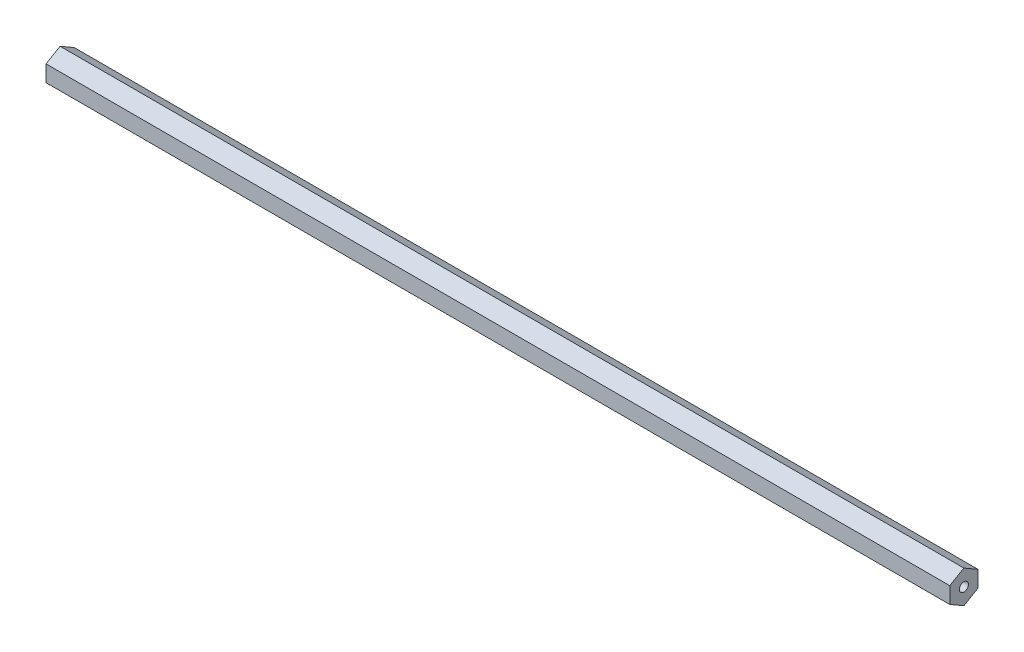
SolidWorks part; units mm, degrees
material "6061-T6 (SS)"
ref_plane "Front" through (0, 0, 0) normal (0, 0, 1) x (1, 0, 0)
ref_plane "Top" through (0, 0, 0) normal (0, 1, 0) x (1, 0, 0)
ref_plane "Right" through (0, 0, 0) normal (1, 0, 0) x (0, 0, -1)
ref_axis "Axis1" through (-80.9, 0, 0) along (1, 0, 0)
sketch "Sketch1" plane through (0, 0, 0) normal (1, 0, 0) x (0, 0, -1)
  line L1 (0, 7.3323) -> (-6.35, 3.6662)
  line L2 (-6.35, 3.6662) -> (-6.35, -3.6662)
  line L3 (-6.35, -3.6662) -> (0, -7.3323)
  line L4 (0, -7.3323) -> (6.35, -3.6662)
  line L5 (6.35, -3.6662) -> (6.35, 3.6662)
  line L6 (6.35, 3.6662) -> (0, 7.3323)
  circle A0 centre (0, 0) radius 6.35 construction
  dimension "D1" = 12.7
extrude "Boss-Extrude1" add sketch "Sketch1" along normal mid plane 406.4
hole_wizard "#10-32 Tapped Hole1" positions "Sketch2" profile "Sketch3" tap size "#10-32" standard "ANSI Inch"
sketch "Sketch2" plane through (203.2, 0, 0) normal (1, 0, 0) x (0, 0, -1)
  point P0 (0, 0)
sketch "Sketch3" plane through (203.2, 0, 0) normal (0, 1, 0) x (0, 0, -1)
  line L0 (0, 0) -> (0, 13.2529)
  line L1 (0, 13.2529) -> (2.0193, 12.0396)
  line L2 (2.0193, 12.0396) -> (2.0193, 0)
  line L5 (2.0193, 0) -> (0, 0)
  line L10 (0, 13.2529) -> (-2.0193, 12.0396) construction
  line L11 (0, -6.35) -> (0, 107.95) construction
  dimension "Tap Drill Dia." = 4.0386
  dimension "Tap Drill Depth" = 12.0396
  dimension "Drill Angle" = 118
cosmetic thread "Hole Thread1" parameters "D1"=9.652, "D2"=4.826
hole_wizard "#10-32 Tapped Hole2" positions "Sketch4" profile "Sketch5" tap size "#10-32" standard "ANSI Inch"
sketch "Sketch4" plane through (-203.2, 0, 0) normal (-1, 0, 0) x (0, 0, 1)
  point P0 (0, 0)
sketch "Sketch5" plane through (-203.2, 0, 0) normal (0, 1, 0) x (0, 0, 1)
  line L0 (0, 0) -> (0, 13.2529)
  line L1 (0, 13.2529) -> (2.0193, 12.0396)
  line L2 (2.0193, 12.0396) -> (2.0193, 0)
  line L5 (2.0193, 0) -> (0, 0)
  line L10 (0, 13.2529) -> (-2.0193, 12.0396) construction
  line L11 (0, -6.35) -> (0, 107.95) construction
  dimension "Tap Drill Dia." = 4.0386
  dimension "Tap Drill Depth" = 12.0396
  dimension "Drill Angle" = 118
cosmetic thread "Hole Thread2" parameters "D1"=9.652, "D2"=4.826
